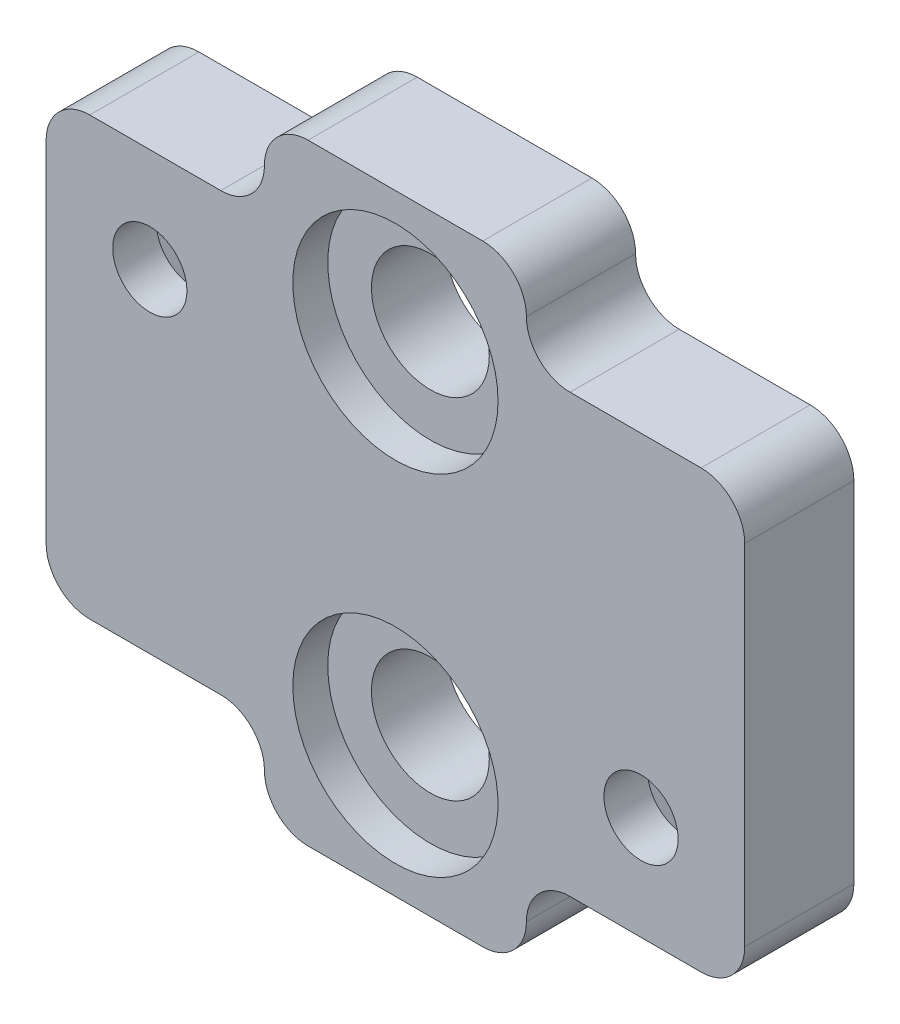
SolidWorks part; units mm, degrees
ref_plane "Piano frontale" through (0, 0, 0) normal (0, 0, 1) x (1, 0, 0)
ref_plane "Piano superiore" through (0, 0, 0) normal (0, 1, 0) x (1, 0, 0)
ref_plane "Piano destro" through (0, 0, 0) normal (1, 0, 0) x (0, 0, -1)
sketch "Schizzo1" plane through (0, 0, 0) normal (0, 0, 1) x (1, 0, 0)
  line L1 (-16, 10) -> (16, 10)
  line L2 (-16, 10) -> (-16, -10)
  line L3 (-16, -10) -> (16, -10)
  line L4 (16, 10) -> (16, -10)
  line L5 (-16, 10) -> (16, -10) construction
  line L6 (-16, -10) -> (16, 10) construction
  point P0 (0, 0)
  dimension "D1" = 32
  dimension "D2" = 20
extrude "Estrusione-Estrusione1" add sketch "Schizzo1" along normal blind 5
sketch "Schizzo2" plane through (0, 0, 5) normal (0, 0, 1) x (1, 0, 0)
  line L1 (-13.9, 7.93) -> (13.9, 7.93) construction
  line L2 (-13.9, 7.93) -> (-13.9, -7.93) construction
  line L3 (-13.9, -7.93) -> (13.9, -7.93) construction
  line L4 (13.9, 7.93) -> (13.9, -7.93) construction
  line L5 (-13.9, 7.93) -> (13.9, -7.93) construction
  line L6 (-13.9, -7.93) -> (13.9, 7.93) construction
  circle A0 centre (-11.25, 5.25) radius 1.7
  circle A1 centre (11.25, -5.25) radius 1.7
  point P0 (0, 0)
  dimension "D5" = 3.4
  dimension "D6" = 3.4
  dimension "D1" = 27.8
  dimension "D2" = 15.86
  dimension "D3" = 22.5
  dimension "D4" = 11.25
  dimension "D7" = 10.5
  dimension "D8" = 5.25
extrude "Taglio-Estrusione1" cut sketch "Schizzo2" against normal through all
sketch "Schizzo3" plane through (0, 0, 0) normal (0, 0, 1) x (1, 0, 0)
  line L0 (16, 10) -> (-16, 10) construction
  line L1 (-6, 10) -> (6, 10)
  line L2 (-6, 10) -> (-6, 14)
  line L3 (-6, 14) -> (6, 14)
  line L4 (6, 10) -> (6, 14)
  line L5 (-16, 0) -> (16, 0) construction
  line L6 (-16, 10) -> (-16, -10) construction
  line L7 (16, -10) -> (16, 10) construction
  line L8 (6, -10) -> (6, -14)
  line L9 (-6, -14) -> (6, -14)
  line L10 (-6, -10) -> (-6, -14)
  line L11 (-6, -10) -> (6, -10)
  point P6 (0, 14)
  point P18 (0, -14)
  dimension "D1" = 12
  dimension "D2" = 4
extrude "Estrusione-Estrusione2" add sketch "Schizzo3" along normal blind 5
sketch "Schizzo4" plane through (0, 0, 5) normal (0, 0, 1) x (1, 0, 0)
  line L0 (-16, 0) -> (16, 0) construction
  line L1 (-16, 10) -> (-16, -10) construction
  line L2 (16, -10) -> (16, 10) construction
  circle A0 centre (0, 8) radius 4.7
  circle A1 centre (0, -8) radius 4.7
  dimension "D1" = 9.4
  dimension "D2" = 8
extrude "Taglio-Estrusione2" cut sketch "Schizzo4" against normal blind 1.6
sketch "Schizzo5" plane through (0, 0, 3.4) normal (0, 0, 1) x (1, 0, 0)
  circle A0 centre (0, 8) radius 2.7
  circle A1 centre (0, -8) radius 2.7
  circle A2 centre (0, 8) radius 4.7 construction
  circle A3 centre (0, -8) radius 4.7 construction
  point P4 (0, 0)
  dimension "D1" = 5.4
extrude "Taglio-Estrusione3" cut sketch "Schizzo5" against normal through all
sketch "Schizzo6" plane through (0, 0, 0) normal (0, 0, -1) x (-1, 0, 0)
  line L1 (7.7859, 5.25) -> (9.5179, 2.25)
  line L2 (9.5179, 2.25) -> (12.9821, 2.25)
  line L3 (12.9821, 2.25) -> (14.7141, 5.25)
  line L4 (14.7141, 5.25) -> (12.9821, 8.25)
  line L5 (12.9821, 8.25) -> (9.5179, 8.25)
  line L6 (9.5179, 8.25) -> (7.7859, 5.25)
  line L7 (-14.7141, -5.25) -> (-12.9821, -8.25)
  line L8 (-12.9821, -8.25) -> (-9.5179, -8.25)
  line L9 (-9.5179, -8.25) -> (-7.7859, -5.25)
  line L10 (-7.7859, -5.25) -> (-9.5179, -2.25)
  line L11 (-9.5179, -2.25) -> (-12.9821, -2.25)
  line L12 (-12.9821, -2.25) -> (-14.7141, -5.25)
  circle A0 centre (11.25, 5.25) radius 3 construction
  circle A1 centre (-11.25, -5.25) radius 3 construction
  point P10 (0, 0)
  point P19 (0, 0)
  dimension "D1" = 6
  dimension "D2" = 6
extrude "Taglio-Estrusione4" cut sketch "Schizzo6" against normal blind 3
fillet "Raccordo1" radius 2 12 edges at (16, 10, 2.5) (16, -10, 2.5) (6, -10, 2.5) (6, -14, 2.5) (-6, -14, 2.5) (-6, -10, 2.5) (-16, -10, 2.5) (-16, 10, 2.5) (6, 14, 2.5) (-6, 14, 2.5) (-6, 10, 2.5) (6, 10, 2.5)
